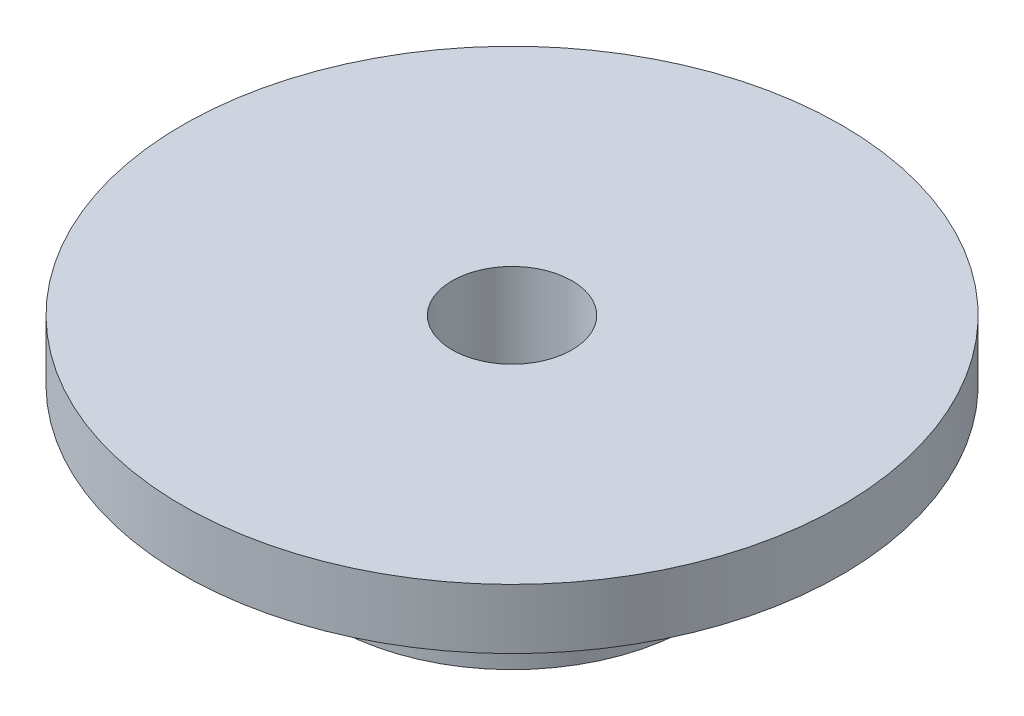
SolidWorks part; units mm, degrees
material "Сталь ШХ15 ГОСТ 801-78"
ref_plane "Plane1" through (0, 0, 0) normal (0, 0, 1) x (1, 0, 0)
ref_plane "Plane2" through (0, 0, 0) normal (0, 1, 0) x (1, 0, 0)
ref_plane "Plane3" through (0, 0, 0) normal (1, 0, 0) x (0, 0, -1)
sketch "Эскиз1" plane through (0, 0, 0) normal (0, 0, 1) x (1, 0, 0)
  line L6 (0, 0) -> (0, 6.4893) construction
  line L7 (2, -0.354) -> (2, 5.646)
  line L8 (2, 5.646) -> (11, 5.646)
  line L9 (11, 5.646) -> (11, 3.646)
  line L10 (11, 3.646) -> (6, 3.646)
  line L11 (6, 3.646) -> (6, -0.354)
  line L12 (6, -0.354) -> (2, -0.354)
  dimension "D1" = 2
  dimension "D2" = 6
  dimension "D3" = 11
  dimension "D4" = 2
  dimension "D5" = 6
revolve "Повернуть1" add sketch "Эскиз1" angle 360 about L6
